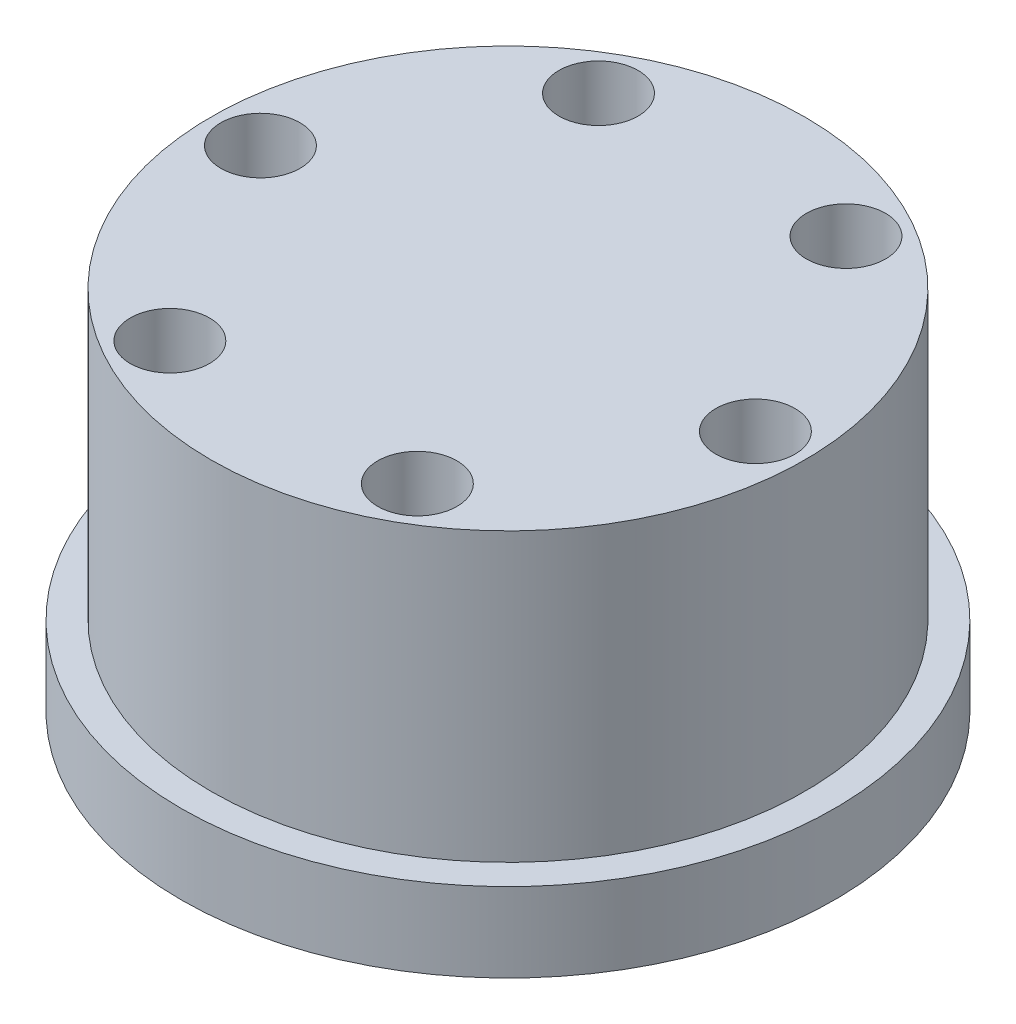
SolidWorks part; units mm, degrees
ref_plane "Front Plane" through (0, 0, 0) normal (0, 0, 1) x (1, 0, 0)
ref_plane "Top Plane" through (0, 0, 0) normal (0, 1, 0) x (1, 0, 0)
ref_plane "Right Plane" through (0, 0, 0) normal (1, 0, 0) x (0, 0, -1)
sketch "Sketch1" plane through (0, 0, 0) normal (0, 1, 0) x (1, 0, 0)
  circle A0 centre (0, 0) radius 16.5
  circle A1 centre (0, 0) radius 12.5 construction
  circle A2 centre (0, 12.5) radius 1.5
  circle A3 centre (10.8253, 6.25) radius 1.5
  circle A4 centre (10.8253, -6.25) radius 1.5
  circle A5 centre (0, -12.5) radius 1.5
  circle A6 centre (-10.8253, -6.25) radius 1.5
  circle A7 centre (-10.8253, 6.25) radius 1.5
  point P19 (0, 0)
  dimension "D1" = 33
  dimension "D2" = 25
  dimension "D3" = 3
  dimension "D4" = 6
extrude "Boss-Extrude1" add sketch "Sketch1" along normal blind 4
sketch "Sketch2" plane through (0, 4, 0) normal (0, 1, 0) x (1, 0, 0)
  circle A0 centre (0, 0) radius 15
  dimension "D1" = 30
extrude "Boss-Extrude2" add sketch "Sketch2" along normal blind 14.5
sketch "Sketch3" plane through (0, 0, 0) normal (0, -1, 0) x (1, 0, 0)
  circle A0 centre (0, 0) radius 9
  dimension "D1" = 18
extrude "Cut-Extrude1" cut sketch "Sketch3" against normal blind 2
sketch "Sketch4" plane through (0, 2, 0) normal (0, -1, 0) x (1, 0, 0)
  circle A0 centre (0, 0) radius 6.5
  dimension "D1" = 13
extrude "Cut-Extrude2" cut sketch "Sketch4" against normal blind 4
sketch "Sketch5" plane through (0, 18.5, 0) normal (0, 1, 0) x (1, 0, 0)
  circle A0 centre (0, 0) radius 12.5 construction
  circle A1 centre (-12.5, 0) radius 2
  circle A2 centre (-6.25, 10.8253) radius 2
  circle A3 centre (6.25, 10.8253) radius 2
  circle A4 centre (12.5, 0) radius 2
  circle A5 centre (6.25, -10.8253) radius 2
  circle A6 centre (-6.25, -10.8253) radius 2
  point P17 (0, 0)
  dimension "D1" = 25
  dimension "D2" = 4
  dimension "D3" = 6
extrude "Cut-Extrude3" cut sketch "Sketch5" against normal blind 6.5
